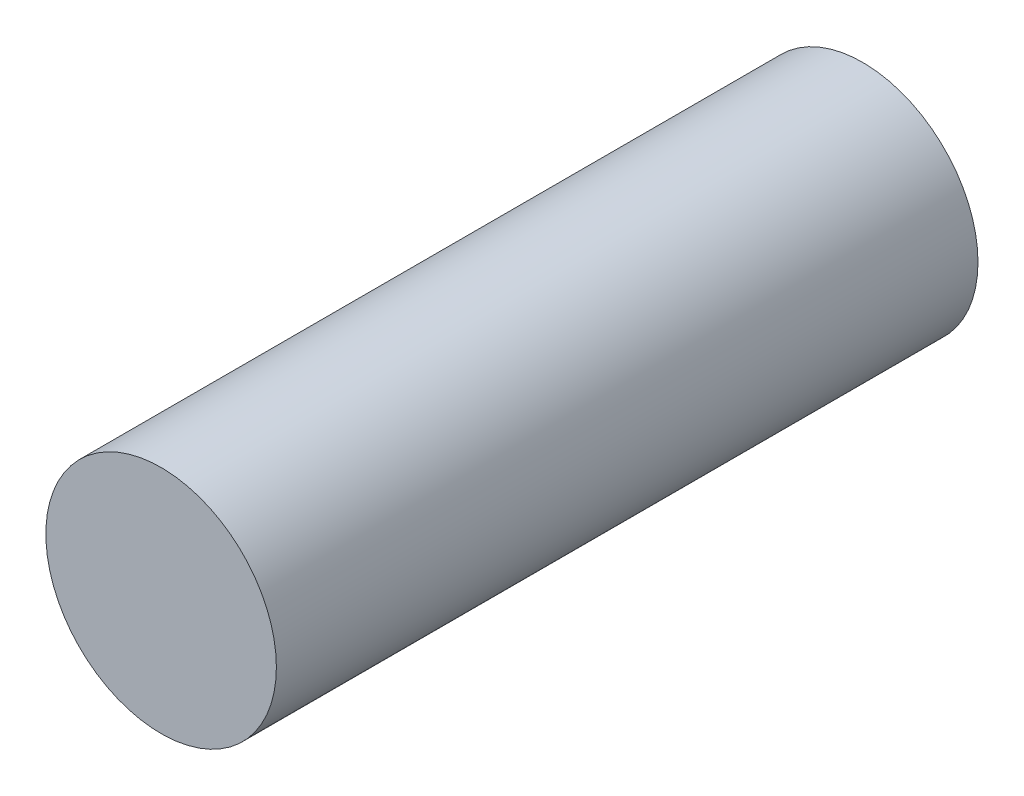
SolidWorks part; units mm, degrees
ref_plane "Front Plane" through (0, 0, 0) normal (0, 0, 1) x (1, 0, 0)
ref_plane "Top Plane" through (0, 0, 0) normal (0, 1, 0) x (1, 0, 0)
ref_plane "Right Plane" through (0, 0, 0) normal (1, 0, 0) x (0, 0, -1)
sketch "Sketch1" plane through (0, 0, 0) normal (0, 0, 1) x (1, 0, 0)
  circle A0 centre (0, 0) radius 2.3
  dimension "D1" = 4.6
extrude "Boss-Extrude1" add sketch "Sketch1" along normal blind 14
